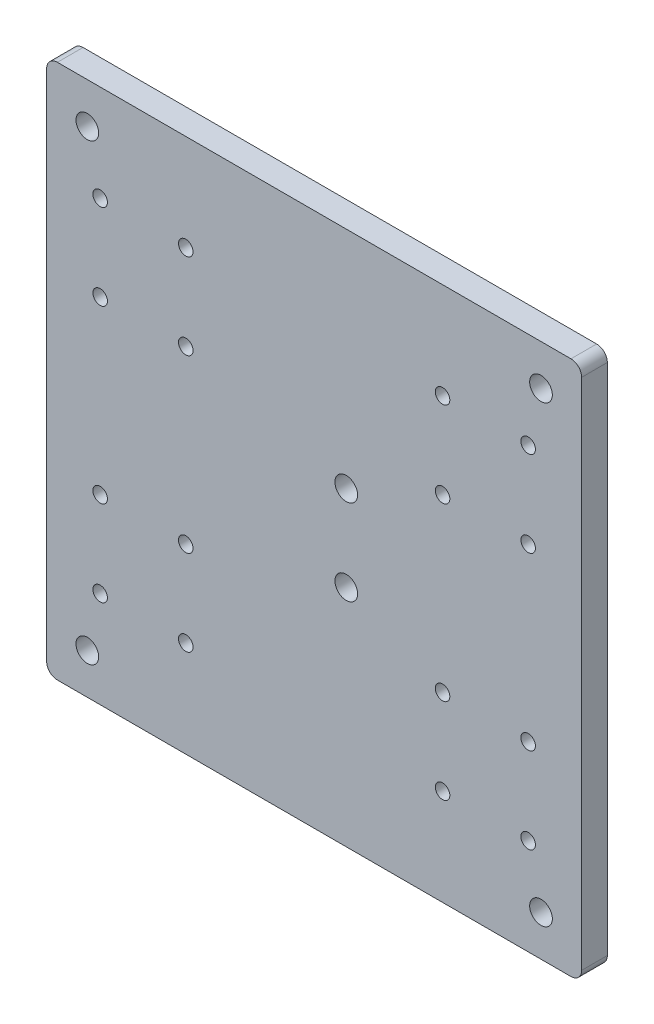
SolidWorks part; units mm, degrees
material "6061-T6 (SS)"
ref_plane "Front Plane" through (0, 0, 0) normal (0, 0, 1) x (1, 0, 0)
ref_plane "Top Plane" through (0, 0, 0) normal (0, 1, 0) x (1, 0, 0)
ref_plane "Right Plane" through (0, 0, 0) normal (1, 0, 0) x (0, 0, -1)
sketch "Sketch1" plane through (0, 0, 0) normal (0, 0, 1) x (1, 0, 0)
  line L0 (-22.5, 62.5) -> (-22.5, -62.5) construction
  line L1 (62.5, -62.5) -> (-62.5, -62.5)
  line L2 (62.5, -62.5) -> (62.5, 62.5)
  line L3 (62.5, 62.5) -> (-62.5, 62.5)
  line L4 (-62.5, -62.5) -> (-62.5, 62.5)
  line L5 (0, 0) -> (0, 62.5) construction
  line L6 (-50, 40) -> (-30, 40) construction
  line L7 (22.5, 62.5) -> (22.5, -62.5) construction
  line L8 (22.5, 0) -> (-22.5, 0) construction
  line L9 (-50, 40) -> (-50, 20) construction
  line L10 (-50, 20) -> (-30, 20) construction
  line L11 (-30, 40) -> (-30, 20) construction
  line L12 (7.5, -10) -> (7.5, 10) construction
  line L14 (-62.5, -62.5) -> (-53, -62.5) construction
  line L15 (-62.5, -62.5) -> (-62.5, -53) construction
  line L16 (-62.5, -53) -> (-53, -53) construction
  line L17 (-53, -62.5) -> (-53, -53) construction
  line L18 (62.5, -62.5) -> (53, -62.5) construction
  line L19 (62.5, -62.5) -> (62.5, -53) construction
  line L20 (62.5, -53) -> (53, -53) construction
  line L21 (53, -62.5) -> (53, -53) construction
  line L22 (62.5, 62.5) -> (53, 62.5) construction
  line L23 (62.5, 62.5) -> (62.5, 53) construction
  line L24 (62.5, 53) -> (53, 53) construction
  line L25 (53, 62.5) -> (53, 53) construction
  line L26 (-62.5, 62.5) -> (-53, 62.5) construction
  line L27 (-62.5, 62.5) -> (-62.5, 53) construction
  line L28 (-62.5, 53) -> (-53, 53) construction
  line L29 (-53, 62.5) -> (-53, 53) construction
  circle A0 centre (-50, 40) radius 1.7
  circle A1 centre (-30, 40) radius 1.7
  circle A2 centre (-30, 20) radius 1.7
  circle A3 centre (-50, 20) radius 1.7
  circle A4 centre (50, 40) radius 1.7
  circle A5 centre (50, 20) radius 1.7
  circle A6 centre (30, 20) radius 1.7
  circle A7 centre (30, 40) radius 1.7
  circle A8 centre (-50, -20) radius 1.7
  circle A9 centre (-30, -20) radius 1.7
  circle A10 centre (-30, -40) radius 1.7
  circle A11 centre (-50, -40) radius 1.7
  circle A12 centre (30, -40) radius 1.7
  circle A13 centre (30, -20) radius 1.7
  circle A14 centre (50, -20) radius 1.7
  circle A15 centre (50, -40) radius 1.7
  circle A16 centre (7.5, 10) radius 2.65
  circle A17 centre (7.5, -10) radius 2.65
  circle A18 centre (-53, -53) radius 2.65
  circle A19 centre (53, -53) radius 2.65
  circle A20 centre (53, 53) radius 2.65
  circle A21 centre (-53, 53) radius 2.65
  point P10 (-40, 40)
  point P13 (0, 0)
  point P15 (0, 62.5)
  point P16 (-50, 30)
  point P55 (7.5, 0)
  dimension "D8" = 3.4
  dimension "D10" = 10
  dimension "D11" = 5.3
  dimension "D14" = 5.3
  dimension "D17" = 5.3
  dimension "D20" = 5.3
  dimension "D23" = 5.3
  dimension "D1" = 125
  dimension "D2" = 125
  dimension "D3" = 45
  dimension "D4" = 17.5
  dimension "D5" = 20
  dimension "D6" = 20
  dimension "D7" = 30
  dimension "D9" = 7.5
  dimension "D12" = 9.5
  dimension "D13" = 9.5
  dimension "D15" = 9.5
  dimension "D16" = 9.5
  dimension "D18" = 9.5
  dimension "D19" = 9.5
  dimension "D21" = 9.5
  dimension "D22" = 9.5
extrude "Boss-Extrude1" add sketch "Sketch1" along normal blind 6
fillet "Fillet1" radius 2.5 4 edges at (-62.5, -62.5, 3) (62.5, -62.5, 3) (62.5, 62.5, 3) (-62.5, 62.5, 3)
sketch "Sketch2" plane through (0, 0, 6) normal (0, 0, 1) x (1, 0, 0)
  point P0 (0, 0)
ref_axis "Axis1" through (0, 0, 0) along (0, 0, 1)
